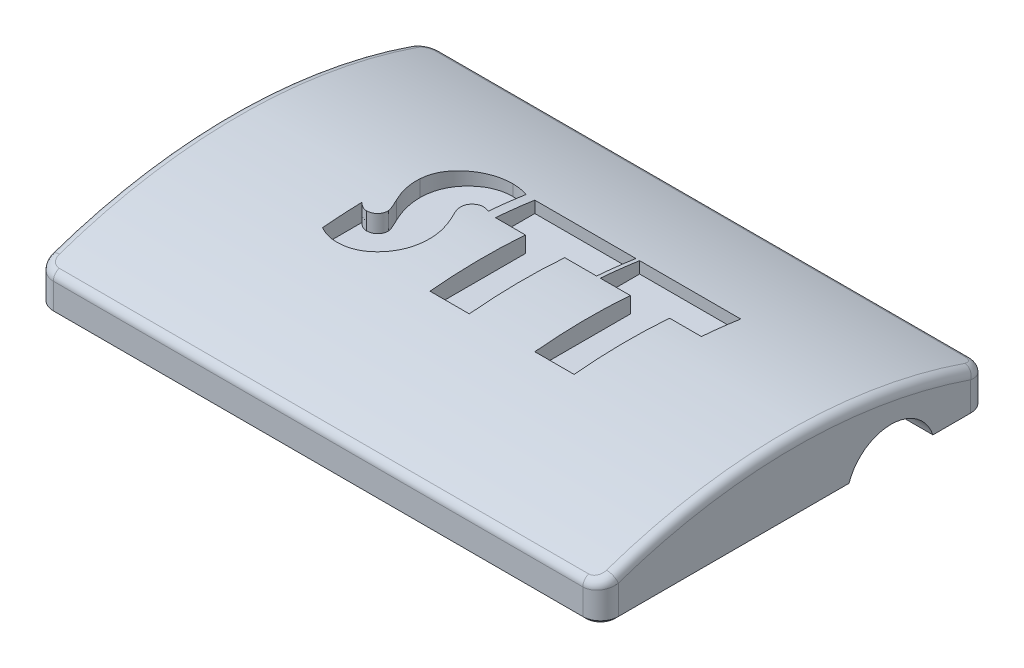
SolidWorks part; units mm, degrees
ref_plane "Front Plane" through (0, 0, 0) normal (0, 0, 1) x (1, 0, 0)
ref_plane "Top Plane" through (0, 0, 0) normal (0, 1, 0) x (1, 0, 0)
ref_plane "Right Plane" through (0, 0, 0) normal (1, 0, 0) x (0, 0, -1)
sketch "Sketch1" plane through (0, 0, 0) normal (0, 1, 0) x (1, 0, 0)
  line L1 (0, 0) -> (31.9, 0)
  line L2 (0, 0) -> (0, 21.9)
  line L3 (0, 21.9) -> (31.9, 21.9)
  line L4 (31.9, 0) -> (31.9, 21.9)
  dimension "D1" = 21.9
  dimension "D2" = 31.9
extrude "Boss-Extrude1" add sketch "Sketch1" along normal blind 2
fillet "Fillet1" radius 1 4 edges at (0, 1, -21.9) (31.9, 1, -21.9) (31.9, 1, 0) (0, 1, 0)
sketch "Sketch2" plane through (0, 2, 0) normal (0, 1, 0) x (1, 0, 0)
  text T0 "STT" font "Bauhaus 93" height in points 24
extrude "Cut-Extrude1" cut sketch "Sketch2" against normal blind 1
sketch "Sketch3" plane through (0, 0, 0) normal (0, -1, 0) x (1, 0, 0)
  line L0 (1, 0) -> (30.9, 0)
  line L1 (31.9, -1) -> (31.9, -20.9)
  line L2 (30.9, -21.9) -> (1, -21.9)
  line L3 (0, -20.9) -> (0, -1)
  line L4 (1.5, -1.5) -> (30.4, -1.5)
  line L5 (30.4, -1.5) -> (30.4, -20.4)
  line L6 (30.4, -20.4) -> (1.5, -20.4)
  line L7 (1.5, -20.4) -> (1.5, -1.5)
  arc A0 (30.9, 0) -> (31.9, -1) centre (30.9, -1) cw
  arc A1 (31.9, -20.9) -> (30.9, -21.9) centre (30.9, -20.9) cw
  arc A2 (1, -21.9) -> (0, -20.9) centre (1, -20.9) cw
  arc A3 (0, -1) -> (1, 0) centre (1, -1) cw
  arc A4 (30.4, -1.5) -> (30.4, -1.5) centre (30.4, -1.5) cw
  arc A5 (30.4, -20.4) -> (30.4, -20.4) centre (30.4, -20.4) cw
  arc A6 (1.5, -20.4) -> (1.5, -20.4) centre (1.5, -20.4) cw
  arc A7 (1.5, -1.5) -> (1.5, -1.5) centre (1.5, -1.5) cw
  dimension "D1" = 1.5
extrude "Boss-Extrude2" add sketch "Sketch3" along normal blind 2
sketch "Sketch4" plane through (0, 0, 0) normal (-1, 0, 0) x (0, 0, 1)
  line L0 (-21.9, -2) -> (-21.9, 2) construction
  line L1 (0, 2) -> (0, -2) construction
  line L2 (-21.9, 0) -> (-21.9, 6.0522)
  line L3 (-21.9, 6.0522) -> (0, 6.0522)
  line L4 (0, 6.0522) -> (0, 0)
  line L5 (-10.95, -2) -> (-10.95, -5.0062) construction
  line L6 (-1, -2) -> (-20.9, -2) construction
  arc A0 (-21.9, 0) -> (0, 0) centre (-10.95, -29.0017) cw
  dimension "D1" = 31
extrude "Cut-Extrude2" cut sketch "Sketch4" against normal through all
sketch "Sketch5" plane through (0, 0, 0) normal (-1, 0, 0) x (0, 0, 1)
  line L0 (-18.9, -4) -> (-18.9, -2.6)
  line L1 (-18.9, -4) -> (-13.9, -4)
  line L2 (-13.9, -4) -> (-13.9, -2.6)
  line L3 (-21.9, -2) -> (-21.9, 0) construction
  line L4 (-1, -2) -> (-20.9, -2) construction
  arc A0 (-13.9, -2.6) -> (-18.9, -2.6) centre (-16.4, -2.6) ccw
  dimension "D1" = 2.5
  dimension "D2" = 3
  dimension "D3" = 2
  dimension "D4" = 1.4
extrude "Cut-Extrude3" cut sketch "Sketch5" against normal through all
fillet "Fillet2" radius 0.5 8 edges at (0.4047, 0.0734, -21.7035) (15.95, 0, -21.9) (31.6567, 0.1284, -21.5537) (31.9, 1.9983, -10.95) (31.4953, 0.0734, -0.1965) (15.95, 0, 0) (0.2433, 0.1284, -0.3463) (0, 1.9983, -10.95)
chamfer "Chamfer1" distance 0.2 angle 45 20 edges at (31.15, -2, -13.9731) (31.15, -2, -18.8269) (30.4, -2, -7.7365) (15.95, -2, -1.5) (1.5, -2, -7.7365) (0.75, -2, -13.9731) (0.75, -2, -18.8269) (31.9, -2, -7.4865) (31.6071, -2, -0.2929) (15.95, -2, 0) (0.2929, -2, -0.2929) (0, -2, -7.4865) (1.5, -2, -19.6135) (15.95, -2, -20.4) (30.4, -2, -19.6135) (0, -2, -19.8635) (0.2929, -2, -21.6071) (15.95, -2, -21.9) (31.6071, -2, -21.6071) (31.9, -2, -19.8635)
